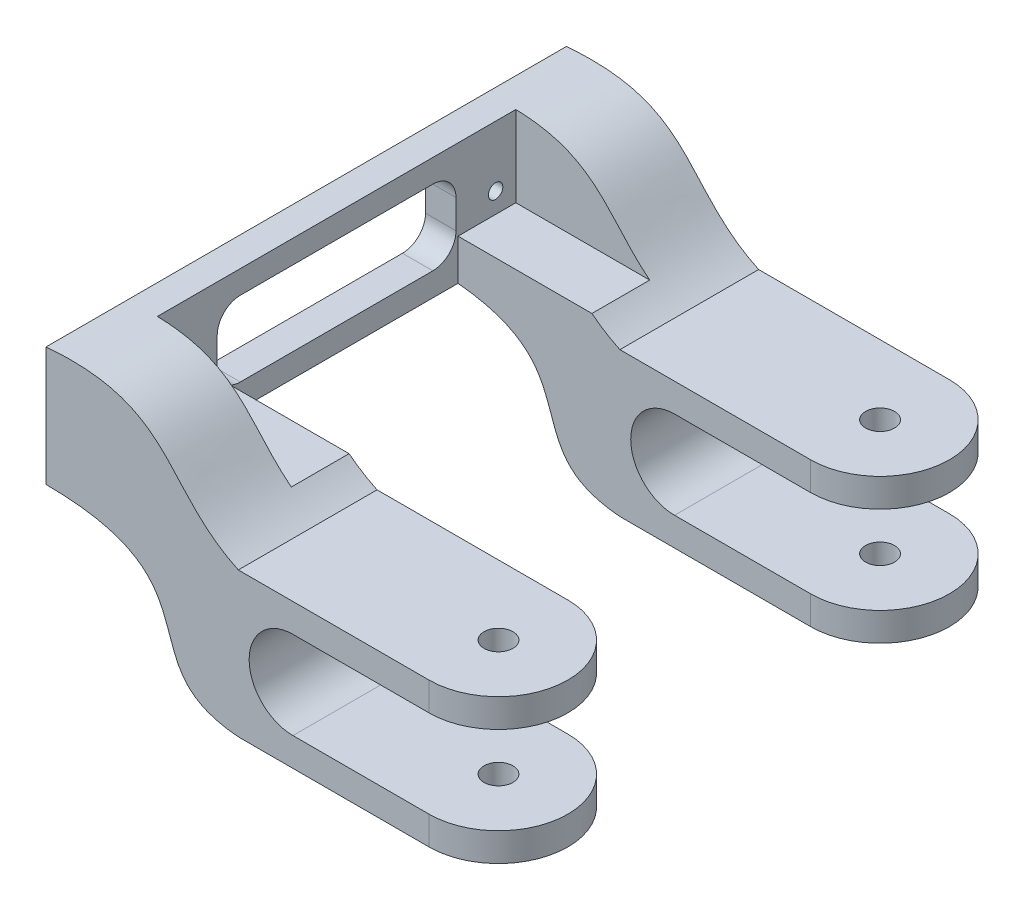
SolidWorks part; units mm, degrees
ref_plane "前视基准面" through (0, 0, 0) normal (0, 0, 1) x (1, 0, 0)
ref_plane "上视基准面" through (0, 0, 0) normal (0, 1, 0) x (1, 0, 0)
ref_plane "右视基准面" through (0, 0, 0) normal (1, 0, 0) x (0, 0, -1)
sketch "Sketch1" plane through (0, 0, 0) normal (0, 0, 1) x (1, 0, 0)
  line L0 (-28.3693, 18.3197) -> (-28.3693, -2.2826)
  line L4 (4.8913, 1.5438) -> (49.8913, 1.5438)
  line L5 (49.8913, 1.5438) -> (49.8913, -3.3746)
  line L6 (49.8913, -3.3746) -> (14.3478, -3.3746)
  line L7 (14.3478, -3.3746) -> (14.3478, -18.5377) construction
  line L8 (14.3478, -18.5377) -> (49.8913, -18.5377)
  line L9 (49.8913, -18.5377) -> (49.8913, -23.4562)
  line L10 (49.8913, -23.4562) -> (5.0158, -23.4562)
  arc A0 (14.3478, -3.3746) -> (14.3478, -18.5377) centre (14.3478, -10.9562) ccw
  spline S0 degree 3 poles (-28.3693, 18.3197) (-6.1653, 20.2708) (-8.3047, 7.7785) (4.8913, 1.5438) knots 0 0 0 0 1 1 1 1
  spline S1 degree 3 poles (-28.3693, -2.2826) (2.684, -2.4309) (-15.2149, -21.9686) (5.0158, -23.4562) knots 0 0 0 0 1 1 1 1
  dimension "D1" = 45
  dimension "D2" = 25
extrude "Boss-Extrude1" add sketch "Sketch1" along normal blind 140
sketch "Sketch2" plane through (0, 1.5438, 0) normal (0, 1, 0) x (1, 0, 0)
  line L0 (67.796, 0) -> (67.796, -140) construction
  line L1 (49.8913, -140) -> (4.8913, -140) construction
  line L2 (49.8913, 0) -> (4.8913, 0) construction
  line L3 (49.8913, -140) -> (49.8913, 0) construction
  line L4 (49.8913, -49) -> (4.8913, -49)
  line L5 (49.8913, -49) -> (49.8913, -91)
  line L6 (49.8913, -91) -> (4.8913, -91)
  line L7 (4.8913, -49) -> (4.8913, -91)
  line L8 (4.8913, -140) -> (4.8913, 0) construction
  line L9 (4.8913, -49) -> (49.8913, -91) construction
  line L10 (49.8913, -49) -> (4.8913, -91) construction
  line L12 (49.8913, -115) -> (4.8913, -115)
  line L13 (49.8913, -115) -> (49.8913, -25)
  line L14 (49.8913, -25) -> (4.8913, -25)
  line L15 (4.8913, -115) -> (4.8913, -25)
  line L16 (49.8913, -115) -> (4.8913, -25) construction
  line L17 (49.8913, -25) -> (4.8913, -115) construction
  line L18 (4.8913, 0) -> (49.8913, 0)
  line L19 (4.8913, 0) -> (4.8913, -25)
  line L20 (4.8913, -25) -> (49.8913, -25)
  line L21 (49.8913, 0) -> (49.8913, -25)
  line L22 (4.8913, -115) -> (49.8913, -115)
  line L23 (4.8913, -115) -> (4.8913, -140)
  line L24 (4.8913, -140) -> (49.8913, -140)
  line L25 (49.8913, -115) -> (49.8913, -140)
  point P14 (49.8913, -70)
  point P15 (67.796, -70)
  point P16 (27.3913, -70)
  line M9 (49.8913, 0) -> (4.8913, 0)
  line M10 (4.8913, 0) -> (4.8913, -140)
  line M11 (4.8913, -140) -> (49.8913, -140)
  line M12 (49.8913, -140) -> (49.8913, 0)
  dimension "D1" = 42
  dimension "D2" = 90
extrude "Cut-Extrude1" cut sketch "Sketch2" against normal through all contours L14 M12 M9 M10 | L6 L4 M12 M10 | L12 M12 M10 M11
sketch "Sketch3" plane through (4.8913, 0, 0) normal (1, 0, 0) x (0, 0, -1)
  line L0 (-115, -3.3746) -> (-115, 1.5438) construction
  line L9 (-140, -23.4467) -> (-115, -23.4467)
  line L10 (-140, -23.4467) -> (-140, 34.9503)
  line L11 (-140, 34.9503) -> (-115, 34.9503)
  line L12 (-115, -23.4467) -> (-115, 34.9503)
  line L13 (0, -23.4467) -> (-25, -23.4467)
  line L14 (0, -23.4467) -> (0, 30.495)
  line L15 (0, 30.495) -> (-25, 30.495)
  line L16 (-25, -23.4467) -> (-25, 30.495)
  line L17 (-25, -3.3746) -> (-25, 1.5438) construction
extrude "Cut-Extrude2" cut sketch "Sketch3" against normal through all
sketch "Sketch4" plane through (0, 1.5438, 0) normal (0, 1, 0) x (1, 0, 0)
  line L0 (49.8913, -25) -> (4.8913, -25) construction
  line L1 (49.8913, -49) -> (4.8913, -49) construction
  line L2 (49.8913, -91) -> (4.8913, -91) construction
  line L3 (49.8913, -115) -> (4.8913, -115) construction
  line L4 (49.8913, -49) -> (49.8913, -25) construction
  line L5 (49.8913, -115) -> (49.8913, -91) construction
  line L8 (37.8913, -25) -> (49.8913, -25)
  line L9 (49.8913, -25) -> (49.8913, -49)
  line L10 (49.8913, -49) -> (37.8913, -49)
  line L11 (37.8913, -91) -> (49.8913, -91)
  line L12 (49.8913, -91) -> (49.8913, -115)
  line L13 (49.8913, -115) -> (37.8913, -115)
  arc A0 (37.8913, -25) -> (37.8913, -49) centre (37.8913, -37) cw
  arc A1 (37.8913, -91) -> (37.8913, -115) centre (37.8913, -103) cw
  line M3 (49.8913, -91) -> (4.8913, -91)
  line M5 (4.8913, -115) -> (49.8913, -115)
  line M6 (49.8913, -115) -> (49.8913, -91)
  dimension "D1" = 12
  dimension "D2" = 12
extrude "Cut-Extrude3" cut sketch "Sketch4" against normal through all contours L8 A0 L9 | A1 L12 M3 | A1 M6 M5 | L9 A0 L10
sketch "Sketch5" plane through (0, 1.5438, 0) normal (0, 1, 0) x (1, 0, 0)
  line L0 (37.8913, -25) -> (4.8913, -25) construction
  circle A0 centre (37.8913, -37) radius 2.5
  circle A1 centre (37.8913, -103) radius 2.5
  arc A2 (37.8913, -49) -> (37.8913, -25) centre (37.8913, -37) ccw construction
  arc A3 (37.8913, -115) -> (37.8913, -91) centre (37.8913, -103) ccw construction
  point P9 (49.8913, -37)
  point P11 (49.8913, -103)
  dimension "D5" = 5
  dimension "D6" = 5
  dimension "D1" = 12
  dimension "D2" = 12
  dimension "D3" = 12
  dimension "D4" = 12
extrude "Cut-Extrude4" cut sketch "Sketch5" against normal through all
sketch "Sketch6" plane through (4.8913, 0, 0) normal (1, 0, 0) x (0, 0, -1)
  line L1 (-91, -23.4467) -> (-49, -23.4467)
  line L2 (-91, -23.4467) -> (-91, 18.5242)
  line L3 (-91, 18.5242) -> (-49, 18.5242)
  line L4 (-49, -23.4467) -> (-49, 18.5242)
  line L6 (-49, -23.4467) -> (-49, 1.5438) construction
  line L7 (-25, 18.5242) -> (-115, 18.5242) construction
extrude "Cut-Extrude5" cut sketch "Sketch6" against normal blind 28
sketch "Sketch7" plane through (-28.3693, 0, 0) normal (-1, 0, 0) x (0, 0, 1)
  line L0 (25, 13.9168) -> (115, 13.9168) construction
  line L1 (25, 18.3197) -> (25, -2.2826) construction
  line L2 (115, -2.2826) -> (115, 18.3197) construction
  line L3 (70, 13.9168) -> (70, 8.0536) construction
  line L4 (42.5, 8.0536) -> (97.5, 8.0536) construction
  circle A0 centre (42.5, 8.0536) radius 1.5
  circle A1 centre (97.5, 8.0536) radius 1.5
  point P11 (70, 8.0536)
  dimension "D2" = 3
  dimension "D3" = 3
  dimension "D1" = 55
hole_wizard "M3 Tapped Hole1" positions "3DSketch1" profile "Sketch8" tap size "M3" standard "GB" end condition through all
sketch3d "3DSketch1"
  point P0 (-28.3693, 8.0536, 42.5)
  point P3 (-28.3693, 8.0536, 97.5)
sketch "Sketch8" plane through (-28.3693, 8.0536, 42.5) normal (0, 1, 0) x (0, 0, 1)
  line L0 (0, 0) -> (0, 78.2606)
  line L1 (0, 78.2606) -> (1.25, 78.2606)
  line L2 (1.25, 78.2606) -> (1.25, 0)
  line L5 (1.25, 0) -> (0, 0)
  line L11 (0, -6.35) -> (0, 107.95) construction
  dimension "Thru Tap Drill Dia." = 2.5
  dimension "Thru Tap Drill Depth" = 78.2606
cosmetic thread "Hole Thread1" parameters "D2"=3
cosmetic thread "Hole Thread2" parameters "D2"=3
sketch "Sketch10" plane through (0, 0, 91) normal (0, 0, -1) x (-1, 0, 0)
  line L0 (-6.0556, 4.5438) -> (23.1087, 4.5438)
  line L1 (23.1087, 18.5147) -> (23.1087, -2.5276) construction
  line L2 (23.1087, 4.5438) -> (23.1087, 21.1564)
  line L3 (23.1087, 21.1564) -> (-12.3855, 21.1564)
  line L4 (-12.3855, 21.1564) -> (-6.0556, 4.5438)
  line L5 (-37.8913, 1.5438) -> (-4.8913, 1.5438) construction
  dimension "D1" = 3
extrude "Cut-Extrude7" cut sketch "Sketch10" against normal blind 10
sketch "Sketch12" plane through (0, 0, 49) normal (0, 0, 1) x (1, 0, 0)
  line L0 (10.2853, 4.5438) -> (-23.1087, 4.5438)
  line L1 (-23.1087, -2.5276) -> (-23.1087, 18.5147) construction
  line L2 (-23.1087, 4.5438) -> (-23.1087, 23.8527)
  line L3 (-23.1087, 23.8527) -> (13.9345, 23.8527)
  line L4 (13.9345, 23.8527) -> (10.2853, 4.5438)
  line L5 (37.8913, 1.5438) -> (4.8913, 1.5438) construction
  dimension "D1" = 3
extrude "Cut-Extrude8" cut sketch "Sketch12" against normal blind 10
sketch "Sketch13" plane through (-28.3693, 0, 0) normal (-1, 0, 0) x (0, 0, 1)
  line L0 (25, 18.3197) -> (115, -2.2826) construction
  line L1 (115, -2.2826) -> (115, 18.3197) construction
  line L2 (115, 18.3197) -> (25, -2.2826) construction
  line L4 (86.6488, 1.5254) -> (53.3512, 1.5254)
  line L5 (90.6488, 5.5254) -> (90.6488, 10.5116)
  line L6 (86.6488, 14.5116) -> (53.3512, 14.5116)
  line L7 (49.3512, 5.5254) -> (49.3512, 10.5116)
  line L8 (90.6488, 1.5254) -> (49.3512, 14.5116) construction
  line L9 (90.6488, 14.5116) -> (49.3512, 1.5254) construction
  arc A0 (90.6488, 10.5116) -> (86.6488, 14.5116) centre (86.6488, 10.5116) ccw
  arc A1 (86.6488, 1.5254) -> (90.6488, 5.5254) centre (86.6488, 5.5254) ccw
  arc A2 (53.3512, 1.5254) -> (49.3512, 5.5254) centre (53.3512, 5.5254) cw
  arc A3 (53.3512, 14.5116) -> (49.3512, 10.5116) centre (53.3512, 10.5116) ccw
  point P4 (70, 8.0185)
  dimension "D1" = 4
extrude "Cut-Extrude9" cut sketch "Sketch13" against normal through all contours A1 L4 A2 L7 A3 L6 A0 L5
